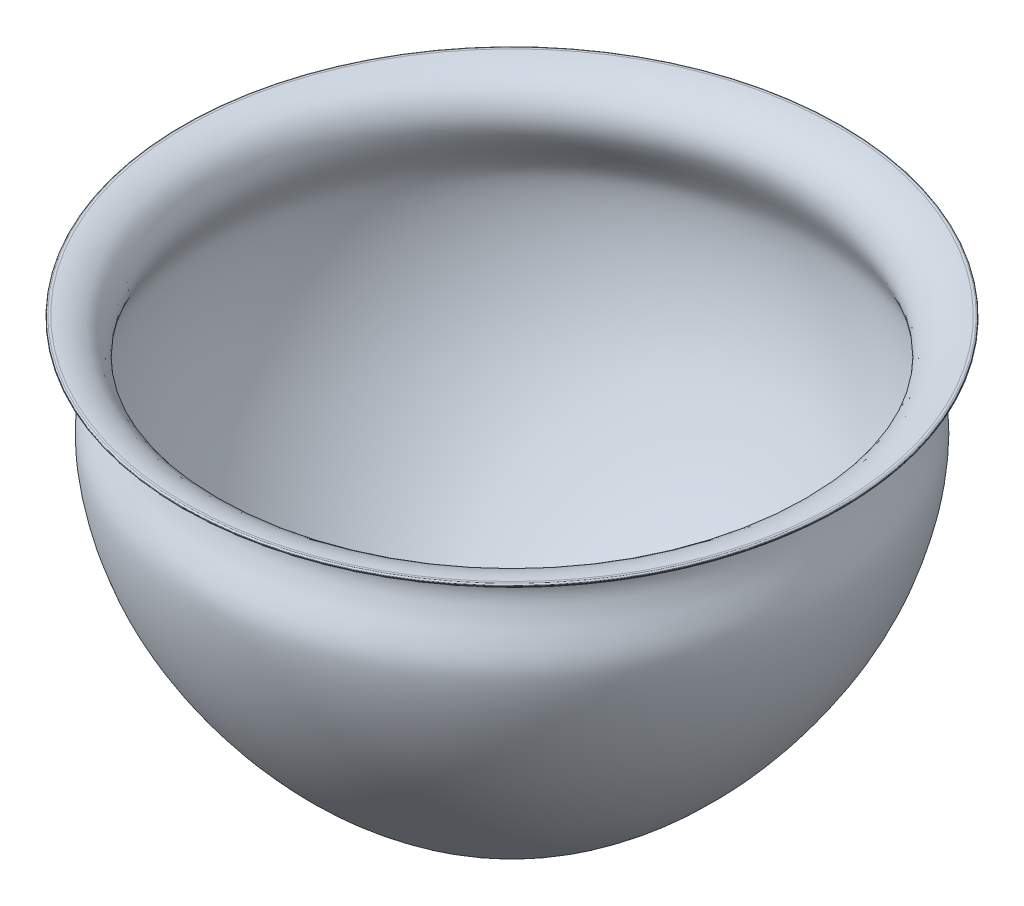
SolidWorks part; units mm, degrees
material "Copper"
ref_plane "Front Plane" through (0, 0, 0) normal (0, 0, 1) x (1, 0, 0)
ref_plane "Top Plane" through (0, 0, 0) normal (0, 1, 0) x (1, 0, 0)
ref_plane "Right Plane" through (0, 0, 0) normal (1, 0, 0) x (0, 0, -1)
sketch "Sketch1" plane through (0, 0, 0) normal (0, 0, 1) x (1, 0, 0)
  line L0 (0, -143.6148) -> (0, 150.3008) construction
  line L1 (0, 0) -> (229.7355, 0) construction
  line L2 (196.85, 110.3852) -> (196.85, 138.1467)
  line L3 (196.85, 138.1467) -> (0, 138.1467)
  line L4 (0, 138.1467) -> (0, -143.6148)
  spline S0 degree 3 poles (0, -143.6148) (21.0972, -140.49) (43.4175, -131.9022) (79.0428, -114.5695) (126.3814, -82.0903) (177.5303, -0.3786) (185.6255, 41.15) (183.5426, 65.7283) (172.9273, 79.9154) (170.4705, 94.0859) (173.9187, 100.9157) (179.35, 106.4306) (187.5488, 110.3852) (196.85, 110.3852) knots 0 0 0 0 0.202767 0.257231 0.512709 0.564297 0.721519 0.753274 0.850088 0.870114 0.933501 0.947282 1 1 1 1
  dimension "D7" = 184.15
  dimension "D1" = 196.85
  dimension "D2" = 254
  dimension "D3" = 19.05
  dimension "D4" = 139.7
  dimension "D5" = 159.1564
  dimension "D6" = 58.42
  dimension "D8" = 171.45
  dimension "D9" = 247.65
  dimension "D10" = 232.41
revolve "Revolve1" add sketch "Sketch1" angle 360 about L4
shell "Shell1" thickness 2 removed face at (0, 138.1467, 196.85)
sketch "Sketch2" plane through (0, 0, 0) normal (0, 0, 1) x (1, 0, 0)
  line L0 (0, 0) -> (0, 225.3841) construction
  line L1 (-228.0688, 150.8727) -> (-184.1577, 150.8727)
  line L2 (-228.0688, 150.8727) -> (-228.0688, 112.3384)
  line L3 (-228.0688, 112.3384) -> (-184.1577, 112.3384)
  line L4 (-184.1577, 150.8727) -> (-184.1577, 112.3384)
  line L5 (194.85, 112.3384) -> (-194.85, 112.3384) construction
revolve "Cut-Revolve1" cut sketch "Sketch2" angle 360 about L0
fillet "Fillet4" radius 0.762 2 edges at (0, 112.3384, 196.85) (0, 110.3852, 196.85)
